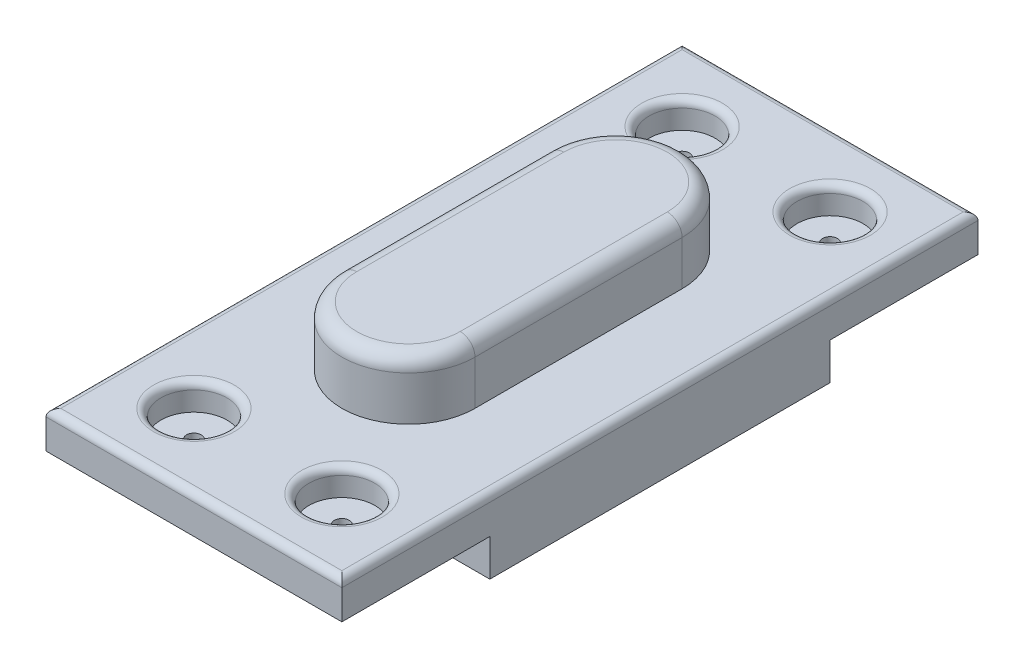
SolidWorks part; units mm, degrees
ref_plane "Front Plane" through (0, 0, 0) normal (0, 0, 1) x (1, 0, 0)
ref_plane "Top Plane" through (0, 0, 0) normal (0, 1, 0) x (1, 0, 0)
ref_plane "Right Plane" through (0, 0, 0) normal (1, 0, 0) x (0, 0, -1)
sketch "Sketch1" plane through (0, 0, 0) normal (0, 1, 0) x (1, 0, 0)
  line L0 (-100, 0) -> (100, 0) construction
  line L1 (-100, -46) -> (100, -46) construction
  line L2 (-100, -46) -> (-100, 46) construction
  line L3 (-100, 46) -> (100, 46) construction
  line L4 (100, -46) -> (100, 46) construction
  line L5 (-100, -46) -> (100, 46) construction
  line L6 (-100, 46) -> (100, -46) construction
  line L7 (0, -46) -> (0, 46) construction
  line L8 (88, -7) -> (88, 7) construction
  line L9 (78, 7) -> (78, -7) construction
  line L10 (-78, 7) -> (-78, -7) construction
  line L11 (-88, -7) -> (-88, 7) construction
  line L12 (78.5, 7) -> (78.5, -7)
  line L13 (87.5, -7) -> (87.5, 7)
  line L14 (93, -21.5) -> (73, -21.5)
  line L15 (93, 0) -> (73, 0)
  line L16 (93, -21.5) -> (93, 21.5)
  line L17 (93, 21.5) -> (73, 21.5)
  line L18 (73, -21.5) -> (73, 21.5)
  line L19 (100, 46) -> (76, 46)
  line L20 (46, 46) -> (46, 76)
  line L21 (46, 46) -> (106, 46)
  line L22 (76, 46) -> (76, 76)
  line L23 (46, 76) -> (106, 76)
  line L24 (106, 46) -> (106, 76)
  arc A0 (88, 7) -> (78, 7) centre (83, 7) ccw construction
  arc A1 (88, -7) -> (78, -7) centre (83, -7) cw construction
  arc A2 (-88, -7) -> (-78, -7) centre (-83, -7) ccw construction
  arc A3 (-88, 7) -> (-78, 7) centre (-83, 7) cw construction
  arc A4 (87.5, 7) -> (78.5, 7) centre (83, 7) ccw
  arc A5 (87.5, -7) -> (78.5, -7) centre (83, -7) cw
  point P0 (0, 0)
  point P9 (0, 0)
  point P12 (0, 0)
  point P16 (83, 12)
  point P19 (88, 0)
  point P21 (78, 0)
  point P45 (0, 0)
  dimension "D9" = 9.5
  dimension "D1" = 92
  dimension "D2" = 200
  dimension "D3" = 12
  dimension "D4" = 10
  dimension "D5" = 12
  dimension "D7" = 5
  dimension "D8" = 5
  dimension "D10" = 24
  dimension "D11" = 30
  dimension "D12" = 30
  dimension "D6" = 0.5
extrude "Boss-Extrude1" add sketch "Sketch1" along normal blind 4 contours A4 L12 A5 L13
extrude "Boss-Extrude2" add sketch "Sketch1<3>" against normal blind 5 separate body contours L13 A5 L12 L15 L18 L14 L16 | A4 L13 L15 L16 L17 L18 L12 | A5 L13 L15 L12 | L13 A4 L12 L15 region at (83, 0, -5.315) region at (83, 0, -12.2873) region at (83, 0, 5.315) region at (83, 0, 12.2873)
sketch "Sketch1<3>" plane through (0, 0, 0) normal (0, 1, 0) x (1, 0, 0) same geometry as "Sketch1"
sketch "Sketch6" plane through (93, 0, 0) normal (1, 0, 0) x (0, 0, -1)
  line L0 (0, -10) -> (0, 0) construction
  line L1 (21.5, -5) -> (11.5, -5)
  line L2 (21.5, -5) -> (21.5, -2.5)
  line L3 (21.5, -2.5) -> (11.5, -2.5)
  line L4 (11.5, -5) -> (11.5, -2.5)
  line L6 (-21.5, -2.5) -> (-11.5, -2.5)
  line L7 (-11.5, -5) -> (-11.5, -2.5)
  line L8 (-21.5, -5) -> (-11.5, -5)
  line L9 (-21.5, -5) -> (-21.5, -2.5)
  point P8 (0, -5)
  dimension "D1" = 10
  dimension "D2" = 2.5
extrude "Cut-Extrude5" cut sketch "Sketch6" against normal up to surface (20 mm away) up to face at (73, -2.5, 0)
sketch "Sketch7" plane through (0, 0, 0) normal (0, 1, 0) x (1, 0, 0)
  line L0 (73, 16.5) -> (93, 16.5) construction
  line L1 (73, -21.5) -> (73, 21.5) construction
  line L2 (93, -21.5) -> (93, 21.5) construction
  line L3 (83, 11.5) -> (83, 21.5) construction
  line L4 (93, 21.5) -> (73, 21.5) construction
  line L5 (93, 0) -> (73, 0) construction
  circle A0 centre (78, 16.5) radius 2.2315
  circle A1 centre (88, 16.5) radius 2.2315
  circle A2 centre (88, -16.5) radius 2.2315
  circle A3 centre (78, -16.5) radius 2.2315
  circle A4 centre (78, 16.5) radius 0.5
  circle A5 centre (88, 16.5) radius 0.5
  circle A6 centre (88, -16.5) radius 0.5
  circle A7 centre (78, -16.5) radius 0.5
  point P13 (83, 16.5)
  dimension "D3" = 1
  dimension "D1" = 5
  dimension "D2" = 5
extrude "Cut-Extrude6" cut sketch "Sketch7" against normal offset from surface (1.8 mm away) 0.7 up to face at (83, -2.5, -16.5)
extrude "Cut-Extrude7" cut sketch "Sketch7<2>" against normal up to surface (2.5 mm away) contours A5 | A7 | A6 | A4 region at (88, 0, -16.5) region at (88, 0, 16.5) region at (78, 0, 16.5) up to face at (83, -2.5, 16.5)
sketch "Sketch7<2>" plane through (0, 0, 0) normal (0, 1, 0) x (1, 0, 0) same geometry as "Sketch7"
fillet "Fillet1" radius 0.5 8 edges at (83, 0, 21.5) (83, 0, -21.5) (78, 0, -14.2685) (88, 0, -18.7315) (88, 0, 18.7315) (78, 0, 14.2685) (73, 0, 0) (93, 0, 0)
fillet "Fillet2" radius 1 4 edges at (83, 4, 11.5) (78.5, 4, 0) (83, 4, -11.5) (87.5, 4, 0)
sketch "Sketch9" plane through (0, -5, 0) normal (0, -1, 0) x (1, 0, 0)
  line L0 (93, 0) -> (73, 0) construction
  line L1 (73, -5.5) -> (90.5, -5.5)
  line L2 (73, -5.5) -> (73, 5.5)
  line L3 (73, 5.5) -> (90.5, 5.5)
  line L4 (90.5, -5.5) -> (90.5, 5.5)
  line L5 (93, 21.5) -> (93, -21.5) construction
  line L6 (73, 21.5) -> (73, -21.5) construction
  line L7 (83, -5.5) -> (83, 5.5) construction
  line L8 (73, 0) -> (93, 0) construction
  circle A1 centre (83, 2.75) radius 0.5
  circle A2 centre (83, -2.75) radius 0.5
  point P0 (83, 0)
  point P11 (90.5, 0)
  point P15 (83, 0)
  point P22 (83, 0)
  dimension "D6" = 1
  dimension "D1" = 2.5
  dimension "D2" = 0
  dimension "D3" = 11
  dimension "D5" = 2.75
extrude "Cut-Extrude8" cut sketch "Sketch9" against normal offset from surface (4 mm away) 1 contours L2 L1 L4 L3 up to face at (83, 0, 0)
extrude "Cut-Extrude9" cut sketch "Sketch9<3>" against normal offset from surface (8 mm away) 1 contours A2 | A1 region at (83, -5, -2.75) up to face at (83, 4, 0)
sketch "Sketch9<3>" plane through (0, -5, 0) normal (0, -1, 0) x (1, 0, 0) same geometry as "Sketch9"
